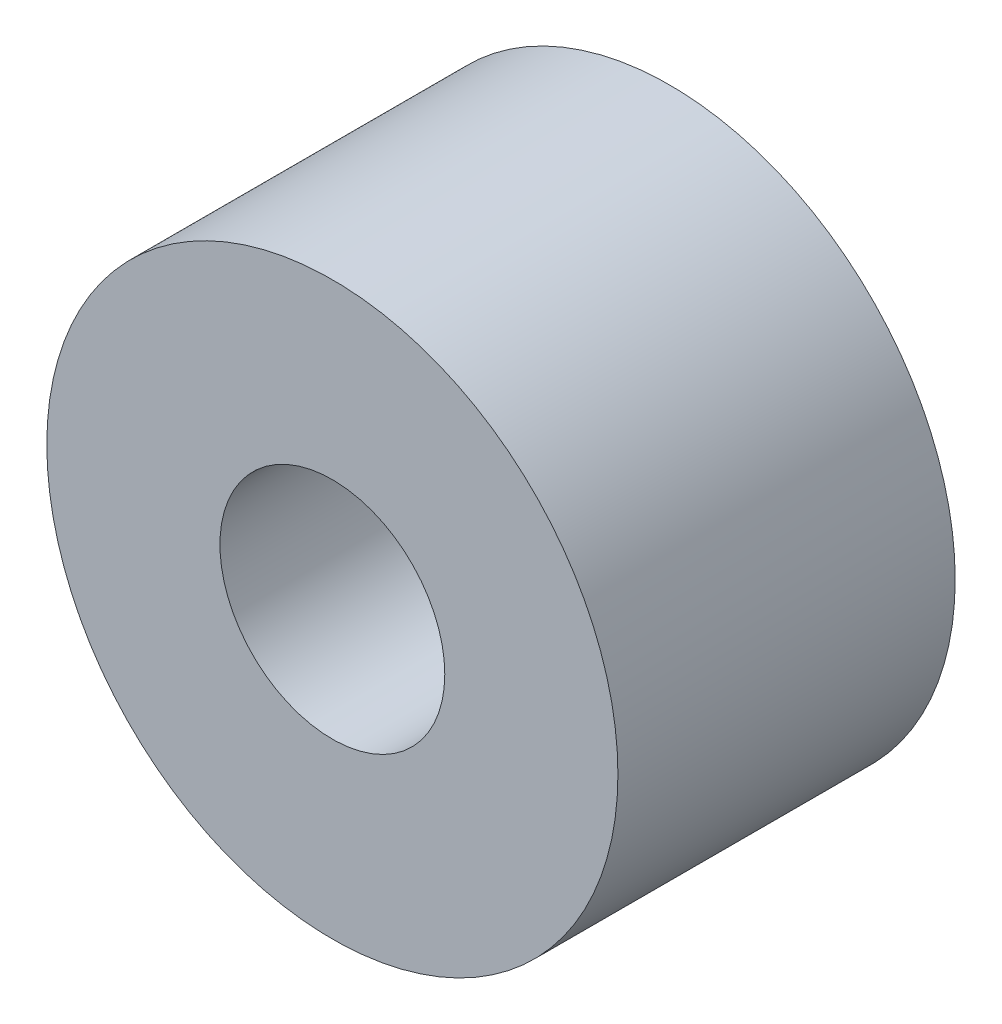
SolidWorks part; units mm, degrees
material "POLYURETHANE (11671)"
ref_plane "Front Plane" through (0, 0, 0) normal (0, 0, 1) x (1, 0, 0)
ref_plane "Top Plane" through (0, 0, 0) normal (0, 1, 0) x (1, 0, 0)
ref_plane "Right Plane" through (0, 0, 0) normal (1, 0, 0) x (0, 0, -1)
sketch "Sketch1" plane through (0, 0, 0) normal (0, 0, 1) x (1, 0, 0)
  circle A0 centre (0, 0) radius 25.4
  dimension "D1" = 50.8
extrude "Boss-Extrude1" add sketch "Sketch1" along normal blind 30
sketch "Sketch2" plane through (0, 0, 30) normal (0, 0, 1) x (1, 0, 0)
  circle A0 centre (0, 0) radius 10
  dimension "D1" = 20
extrude "Cut-Extrude1" cut sketch "Sketch2" against normal through all contours A0
